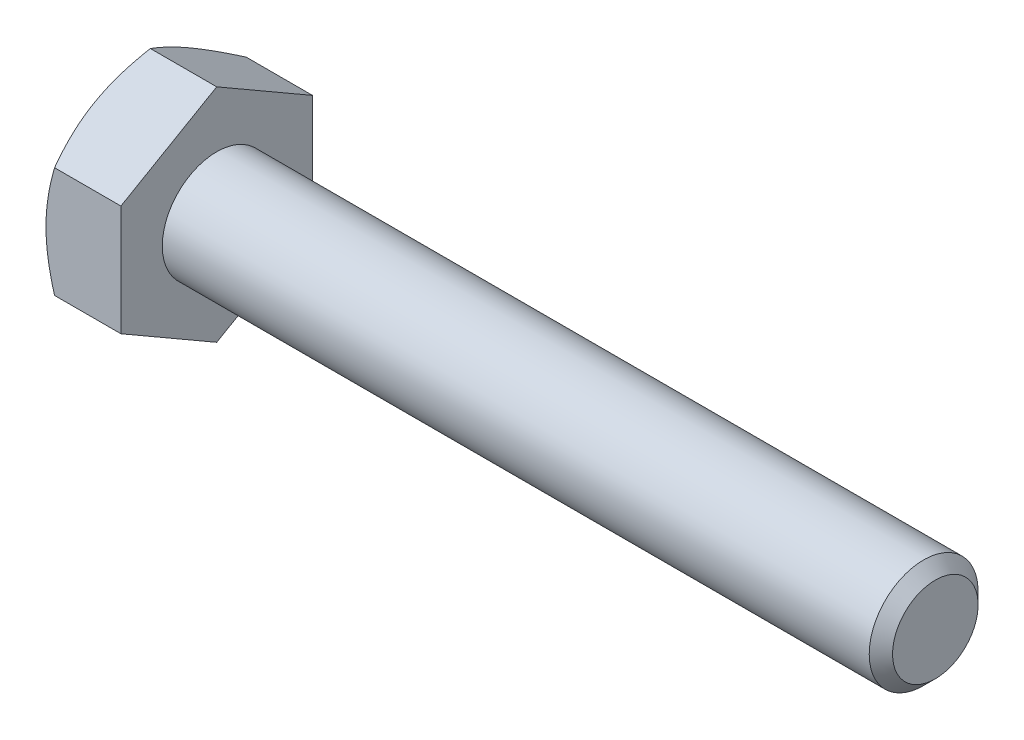
SolidWorks part; units mm, degrees
material "Alloy Steel (SS)"
ref_plane "Front Plane" through (0, 0, 0) normal (0, 0, 1) x (1, 0, 0)
ref_plane "Top Plane" through (0, 0, 0) normal (0, 1, 0) x (1, 0, 0)
ref_plane "Right Plane" through (0, 0, 0) normal (1, 0, 0) x (0, 0, -1)
sketch "Sketch1" plane through (0, 0, 0) normal (0, 0, 1) x (1, 0, 0)
  line L0 (-23.1394, 0) -> (23.1394, 0) construction
  line L1 (23.1394, 3.175) -> (23.1394, -3.175) construction
  line L2 (-18.7706, 5.588) -> (-18.7706, -5.588) construction
  line L3 (-23.1394, 5.588) -> (-23.1394, -5.588) construction
  point P9 (-18.7706, 0)
  point P10 (19.9644, -3.175)
  dimension "Screw Dia" = 6.35
  dimension "Hex" = 11.176
  dimension "Head Ht" = 4.3688
  dimension "Screw Lenght" = 41.91
  dimension "D1" = 3.175
ref_plane "Plane2" through (23.1394, 0, 0) normal (1, 0, 0) x (0, 0, -1)
sketch "Sketch5" plane through (23.1394, 0, 0) normal (1, 0, 0) x (0, 0, -1)
  circle A0 centre (0, 0) radius 3.175
extrude "Boss-Extrude3" add sketch "Sketch5" against normal up to vertex (41.91 mm away) up to point (-18.7706, 0, 0)
sketch "Sketch9" plane through (23.1394, 0, 0) normal (1, 0, 0) x (0, 0, -1)
  circle A1 centre (0, 0) radius 3.175
  circle A2 centre (0, 0) radius 3.175
  dimension "D1" = 0
curve "Helix/Spiral1" [suppressed] pitch 0.9071 height 35.814 turns 39.48 parameters "Pitch"=0.9071
chamfer "Chamfer1" distance 0.6804 angle 45 1 edges at (23.1394, 0, -3.175)
sketch "Sketch10" plane through (0, 0, 0) normal (0, 0, 1) x (1, 0, 0)
  line L0 (22.7425, 3.175) -> (23.0827, 2.5858)
  line L1 (23.0827, 2.5858) -> (23.1961, 2.5858)
  line L2 (23.1961, 2.5858) -> (23.5363, 3.175)
  line L3 (22.7425, 3.175) -> (23.5363, 3.175)
  line L4 (23.1394, 3.175) -> (23.1394, 2.5858) construction
  line L5 (22.9126, 2.8804) -> (23.3662, 2.8804) construction
  dimension "D1" = 60
  dimension "D2" = 0.1134
  dimension "D3" = 0.4536
sweep "Cut-Sweep1" [suppressed] cut profiles "Sketch10" path "Helix/Spiral1"
sketch "Sketch11" plane through (0, 0, 0) normal (0, 0, 1) x (1, 0, 0)
  line L0 (-18.7706, 3.175) -> (-18.7706, 0)
  line L1 (-18.7706, 0) -> (13.0599, 0)
  line L2 (13.0599, 0) -> (11.2268, 3.175)
  line L4 (-18.7706, 3.175) -> (11.2268, 3.175)
  dimension "D1" = 60
  dimension "D2" = 11.9126
revolve "Revolve1" [suppressed] add sketch "Sketch11" angle 360 about L1
sketch "Sketch6" plane through (-18.7706, 0, 0) normal (-1, 0, 0) x (0, 0, 1)
  line L0 (0, 5.588) -> (0, -5.588) construction
  line L1 (5.588, 3.2262) -> (0, 6.4525)
  line L2 (0, 6.4525) -> (-5.588, 3.2262)
  line L3 (-5.588, 3.2262) -> (-5.588, -3.2262)
  line L4 (-5.588, -3.2262) -> (0, -6.4525)
  line L5 (0, -6.4525) -> (5.588, -3.2262)
  line L6 (5.588, -3.2262) -> (5.588, 3.2262)
  circle A0 centre (0, 0) radius 5.588 construction
extrude "Boss-Extrude4" add sketch "Sketch6" along normal up to vertex (4.3688 mm away) up to point (-23.1394, -5.588, 0)
sketch "Sketch8" plane through (-23.1394, 0, 0) normal (-1, 0, 0) x (0, 0, 1)
  circle A0 centre (0, 0) radius 5.588 construction
  circle A1 centre (0, 0) radius 5.588
extrude "Cut-Extrude3" cut sketch "Sketch8" against normal through all draft 60 flip side to cut
sketch "Sketch13" plane through (-23.1394, 0, 0) normal (-1, 0, 0) x (0, 0, 1)
  line L0 (0, 0) -> (-1.8627, 0) construction
  line L1 (-3.7253, -1.8627) -> (-1.8627, -1.8627)
  line L2 (-3.7253, -1.8627) -> (-3.7253, -2.794)
  line L3 (-3.7253, -2.794) -> (-1.8627, -2.794)
  line L4 (-1.8627, -1.8627) -> (-1.8627, -2.794)
  line L5 (-1.8627, 0) -> (-3.7253, 0) construction
  line L6 (-3.7253, 0) -> (-5.588, 0) construction
  line L7 (-1.8627, 0) -> (-1.8627, -1.8627) construction
  line L8 (-3.7253, -1.8627) -> (-3.7253, 0) construction
  line L9 (-2.794, -1.8627) -> (-1.8627, -1.8627) construction
extrude "Cut-Extrude4" [suppressed] cut sketch "Sketch13" against normal blind 0.254
equation "\"D2@Sketch10\" = \"Pitch@Helix/Spiral1\"*.125"
equation "\"D3@Sketch10\" = \"Pitch@Helix/Spiral1\"*.5"
equation "\"D1@Chamfer1\" = \"Pitch@Helix/Spiral1\"*.75"
equation "\"D1@Sketch1\" = \"Pitch@Helix/Spiral1\"*3.5"
